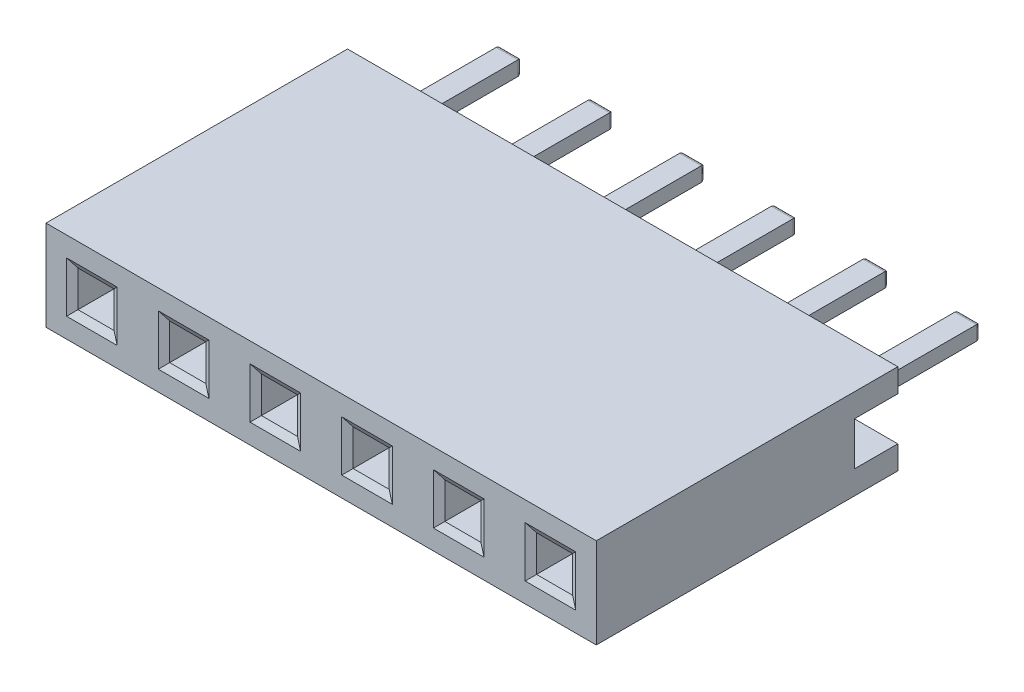
SolidWorks part; units mm, degrees
material "PET"
ref_plane "Front Plane" through (0, 0, 0) normal (0, 0, 1) x (1, 0, 0)
ref_plane "Top Plane" through (0, 0, 0) normal (0, 1, 0) x (1, 0, 0)
ref_plane "Right Plane" through (0, 0, 0) normal (1, 0, 0) x (0, 0, -1)
sketch "Sketch1" plane through (0, 0, 0) normal (0, 0, 1) x (1, 0, 0)
  line L0 (-1.25, 0) -> (0.02, 0) construction
  line L1 (1.29, -1.25) -> (-1.25, -1.25)
  line L2 (1.29, -1.25) -> (1.29, 1.25)
  line L3 (1.29, 1.25) -> (-1.25, 1.25)
  line L4 (-1.25, -1.25) -> (-1.25, 1.25)
  line L5 (0.02, 0) -> (1.29, 0) construction
  line L9 (0.52, -0.5) -> (-0.48, -0.5)
  line L10 (0.52, -0.5) -> (0.52, 0.5)
  line L11 (0.52, 0.5) -> (-0.48, 0.5)
  line L12 (-0.48, -0.5) -> (-0.48, 0.5)
  line L13 (0.52, -0.5) -> (-0.48, 0.5) construction
  line L14 (0.52, 0.5) -> (-0.48, -0.5) construction
  point P0 (0, 0)
  point P10 (0.02, 0)
  dimension "D1" = 2.5
  dimension "D2" = 2.54
  dimension "D5" = 1
  dimension "D6" = 1
extrude "Boss-Extrude1" add sketch "Sketch1" along normal blind 8.35
chamfer "Chamfer1" distance 0.2 angle 30 4 edges at (0.52, 0, 8.35) (0.02, 0.5, 8.35) (-0.48, 0, 8.35) (0.02, -0.5, 8.35) first distance on face at (0.02, 0, 8.35)
pattern_linear "LPattern2" count 6 spacing 2.54 along (1, 0, 0) of "Boss-Extrude1", "Chamfer1"
sketch "Sketch4" plane through (-1.25, 0, 0) normal (-1, 0, 0) x (0, 0, 1)
  line L0 (0, 1.25) -> (0, -1.25) construction
  line L1 (0, -0.6) -> (1.2, -0.6)
  line L2 (0, -0.6) -> (0, 0.6)
  line L3 (0, 0.6) -> (1.2, 0.6)
  line L4 (1.2, -0.6) -> (1.2, 0.6)
  point P6 (0, 0)
  point P7 (0, 0)
  dimension "D1" = 1.2
  dimension "D2" = 1.2
extrude "Cut-Extrude1" cut sketch "Sketch4" against normal through all
sketch "Sketch3" plane through (0, 0, 1.2) normal (0, 0, -1) x (-1, 0, 0)
  line L1 (-11.72, -0.2) -> (-13.72, -0.2)
  line L2 (-11.72, -0.2) -> (-11.72, 0.2)
  line L3 (-11.72, 0.2) -> (-13.72, 0.2)
  line L4 (-13.72, -0.2) -> (-13.72, 0.2)
  line L5 (-11.72, -0.2) -> (-13.72, 0.2) construction
  line L6 (-11.72, 0.2) -> (-13.72, -0.2) construction
  line L8 (-13.22, 0) -> (-12.22, 0) construction
  line L9 (-12.72, 0.6) -> (-12.72, -0.6) construction
  line L11 (-13.99, -0.6) -> (1.25, -0.6) construction
  line L12 (-13.02, 0.2) -> (-12.42, 0.2)
  line L13 (-13.02, 0.2) -> (-13.02, -0.2)
  line L14 (-13.02, -0.2) -> (-12.42, -0.2)
  line L15 (-12.42, 0.2) -> (-12.42, -0.2)
  line L16 (-13.99, 0.6) -> (1.25, 0.6) construction
  line L18 (-13.22, -0.5) -> (-13.22, 0.5) construction
  line L19 (-12.22, 0.5) -> (-12.22, -0.5) construction
  point P0 (-12.72, 0)
  point P5 (-8.9514, -0.6)
  point P8 (-12.72, 0)
  point P13 (0, 0)
  point P20 (0, 0)
  point P21 (0, 0)
  point P23 (0, 0)
  point P24 (-11.3108, 0)
  point P26 (0, 0)
  point P29 (0, 0)
  point P30 (-12.72, 0)
  dimension "D1" = 0.4
  dimension "D2" = 2
  dimension "D3" = 0.6
extrude "Boss-Extrude2" add sketch "Sketch3" along normal blind 0.2 from surface contours L13 L3 L4 L1 | L3 L15 L1 L2 | L15 L3 L13 L1 region at (12.07, 0, 1.2) region at (12.72, 0, 1.2) region at (13.37, 0, 1.2) starting at face at (0.02, 0, 1.2)
extrude "Boss-Extrude3" add sketch "Sketch3<3>" along normal blind 4.45 contours L15 L3 L13 L1 region at (12.72, 0, 1.2)
sketch "Sketch3<3>" plane through (0, 0, 1.2) normal (0, 0, -1) x (-1, 0, 0) same geometry as "Sketch3"
fillet "Fillet1" radius 0.1 4 edges at (12.72, -0.2, -3.25) (13.02, 0, -3.25) (12.72, 0.2, -3.25) (12.42, 0, -3.25)
fillet "Fillet2" radius 0.25 4 edges at (13.02, 0, 1) (12.42, 0, 1) (11.72, 0, 1) (13.72, 0, 1)
pattern_linear "LPattern3" count 6 spacing 2.54 along (-1, 0, 0) of "Boss-Extrude2", "Boss-Extrude3", "Fillet1", "Fillet2"
